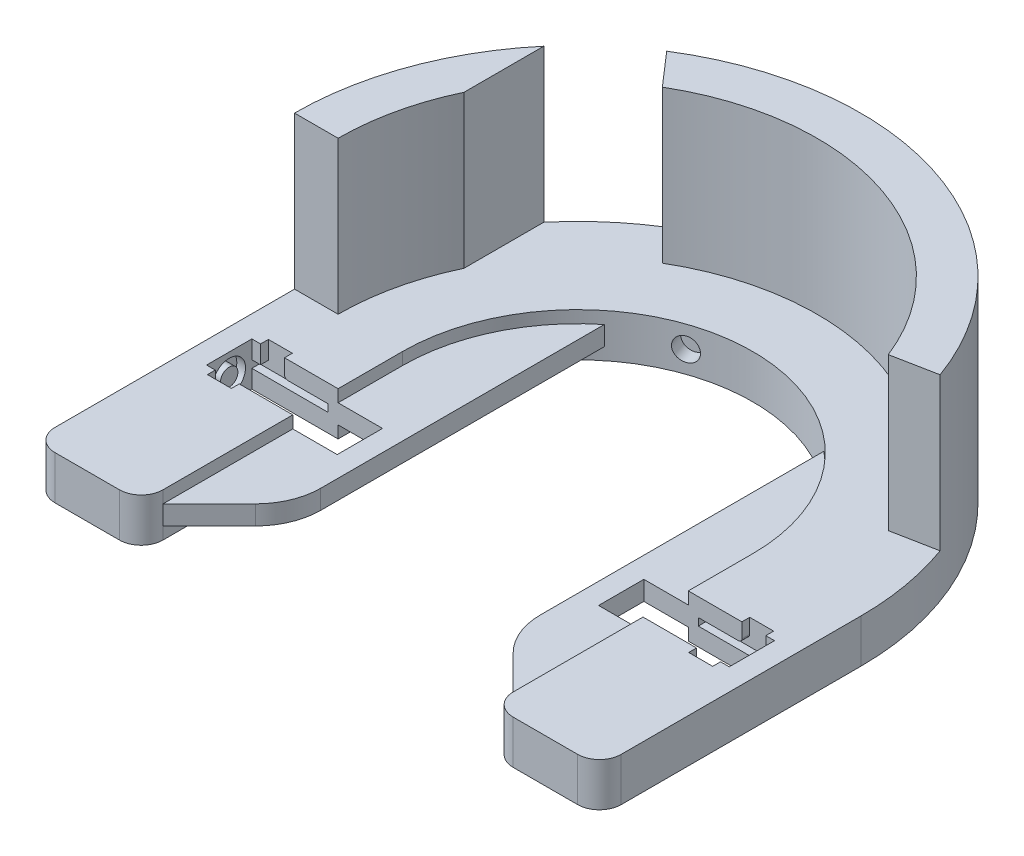
SolidWorks part; units mm, degrees
ref_plane "Front Plane" through (0, 0, 0) normal (0, 0, 1) x (1, 0, 0)
ref_plane "Top Plane" through (0, 0, 0) normal (0, 1, 0) x (1, 0, 0)
ref_plane "Right Plane" through (0, 0, 0) normal (1, 0, 0) x (0, 0, -1)
sketch "Sketch3" plane through (0, 0, 0) normal (0, 1, 0) x (1, 0, 0)
  line L0 (65, 0) -> (65, -55)
  line L1 (-65, 0) -> (65, 0) construction
  line L2 (60, -60) -> (45.2, -60)
  line L3 (40.2, -55) -> (40.2, 0)
  line L4 (25.2, -33.7868) -> (25.2, 31.3209)
  line L5 (29.5934, -44.3934) -> (40.2, -55)
  line L6 (54.9988, 0) -> (54.9988, -60)
  line L7 (0, -55) -> (0, 55) construction
  line L8 (-54.9988, 0) -> (-54.9988, -60)
  line L9 (-29.5934, -44.3934) -> (-40.2, -55)
  line L10 (-25.2, -33.7868) -> (-25.2, 31.3209)
  line L11 (-40.2, -55) -> (-40.2, 0)
  line L12 (-60, -60) -> (-45.2, -60)
  line L13 (-65, 0) -> (-65, -55)
  arc A0 (65, 0) -> (-65, 0) centre (0, 0) ccw
  arc A1 (40.2, 0) -> (-40.2, 0) centre (0, 0) ccw
  arc A2 (60, -60) -> (65, -55) centre (60, -55) ccw
  arc A3 (45.2, -60) -> (40.2, -55) centre (45.2, -55) cw
  arc A4 (25.2, -33.7868) -> (29.5934, -44.3934) centre (40.2, -33.7868) ccw
  arc A5 (-54.9988, 0) -> (54.9988, 0) centre (0, 0) cw
  arc A6 (-25.2, -33.7868) -> (-29.5934, -44.3934) centre (-40.2, -33.7868) cw
  arc A7 (-45.2, -60) -> (-40.2, -55) centre (-45.2, -55) ccw
  arc A8 (-60, -60) -> (-65, -55) centre (-60, -55) cw
  point P12 (65, -60)
  point P16 (40.2, -60)
  point P19 (25.2, -40)
  point P37 (-25.2, -40)
  point P38 (-40.2, -60)
  point P39 (-65, -60)
  dimension "130" = 130
  dimension "D4" = 80.4
  dimension "D8" = 5
  dimension "D9" = 15
  dimension "D10" = 54.9988
  dimension "D2" = 60
  dimension "D3" = 24.8
  dimension "D5" = 15
  dimension "D6" = 5
  dimension "D7" = 15
extrude "Boss-Extrude1" add sketch "Sketch3" along normal mid plane 4.4 contours A1 L1 L10 | L1 L11 L9 A6 L10 | L4 L1 A1 | L1 L4 A4 L5 L3 region at (33.1426, 0, 23.8401) region at (31.3077, 0, -12.105) region at (-31.3077, 0, -12.105) region at (-33.1426, 0, 23.8401)
extrude "Boss-Extrude2" add sketch "Sketch3<3>" along normal mid plane 10 contours A5 L1 A1 | L1 L3 A3 L2 L6 | L1 L8 L12 A7 L11 region at (47.6376, 0, 29.8244) region at (47.5994, 0, -1.2298) region at (-47.6376, 0, 29.8244)
sketch "Sketch3<3>" plane through (0, 0, 0) normal (0, 1, 0) x (1, 0, 0) same geometry as "Sketch3"
extrude "Boss-Extrude3" add sketch "Sketch3<4>" against normal blind 5 and the other way blind 40 contours A0 L1 A5 | L1 L13 A8 L12 L8 | L1 L6 L2 A2 L0 region at (59.9643, 0, 29.7394) region at (59.9994, 0, -1.4534) region at (-59.9643, 0, 29.7394)
sketch "Sketch3<4>" plane through (0, 0, 0) normal (0, 1, 0) x (1, 0, 0) same geometry as "Sketch3"
sketch "Sketch4" plane through (0, 0, 0) normal (1, 0, 0) x (0, 0, -1)
  line L0 (-45, 5) -> (-60, 5)
  line L1 (-60, 5) -> (-60, 40)
  line L2 (-60, 40) -> (0, 40)
  line L3 (0, -5) -> (-55, -5) construction
  line L4 (0, 40) -> (-55, 40) construction
  line L5 (-60, 40) -> (-60, -5) construction
  arc A0 (-45, 5) -> (0, 40) centre (0, -6.4286) cw
  dimension "D2" = 15
  dimension "D1" = 10
extrude "Cut-Extrude1" cut sketch "Sketch4" against normal through all both and the other way through all
sketch "Sketch5" plane through (0, 40, 0) normal (0, 1, 0) x (1, 0, 0)
  line L0 (0, 0) -> (-42.6438, 49.0561) construction
  line L2 (-49.6832, 41.9115) -> (-43.0281, 34.2556) construction
  line L4 (-34.5891, 55.0327) -> (-27.9339, 47.3768)
  line L5 (0, 0) -> (0, 65) construction
  line L6 (-49.6832, 41.9115) -> (-49.6832, 23.5889)
  line L7 (0, 0) -> (63.8058, 12.4026) construction
  line L8 (51.1803, 20.1356) -> (61.1381, 22.0712)
  line L9 (54.9988, 0) -> (54.9988, -45)
  line L10 (54.9988, -45) -> (65, -45)
  line L11 (65, -45) -> (65, 0)
  line L12 (65, -45) -> (65, 0) construction
  line L13 (54.9988, 0) -> (54.9988, -45) construction
  line L14 (54.9988, -45) -> (65, -45) construction
  line L16 (-65, -45) -> (-54.9988, -45)
  line L17 (-65, -45) -> (-65, 0)
  line L18 (-65, 0) -> (-54.9988, 0)
  line L19 (-54.9988, -45) -> (-54.9988, 0)
  arc A0 (65, 0) -> (-65, 0) centre (0, 0) ccw construction
  arc A1 (-49.6832, 41.9115) -> (-34.5891, 55.0327) centre (0, 0) cw
  arc A2 (-43.0281, 34.2556) -> (-27.9339, 47.3768) centre (0, 0) cw
  arc A3 (54.9988, 0) -> (-54.9988, 0) centre (0, 0) ccw construction
  arc A4 (-49.6832, 23.5889) -> (-43.0281, 34.2556) centre (0, 0) cw
  arc A5 (54.9988, 0) -> (-54.9988, 0) centre (0, 0) ccw construction
  arc A6 (61.1381, 22.0712) -> (65, 0) centre (0, 0) cw
  arc A7 (51.1803, 20.1356) -> (54.9988, 0) centre (0, 0) cw
  point P40 (-58.0676, -39.3853)
  point P41 (0, 0)
  dimension "D2" = 20
  dimension "D3" = 10
  dimension "D4" = 120
  dimension "D1" = 41
  dimension "D6" = 10
extrude "Cut-Extrude2" cut sketch "Sketch5" against normal blind 35
ref_axis "Axis1" through (0, 42.25, 0) along (0, -1, 0)
ref_plane "Plane1" through (0, 0, 0) normal (0.3256, 0, 0.9455) x (0, -1, 0)
sketch "Sketch6" plane through (0, 0, 0) normal (0.3256, 0, 0.9455) x (0, -1, 0)
  circle A0 centre (0, 0) radius 2.625
  dimension "D1" = 5.25
extrude "Cut-Extrude3" cut sketch "Sketch6" against normal blind 43.5
sketch "Sketch7" plane through (0, 5, 0) normal (0, 1, 0) x (1, 0, 0)
  line L0 (65, -55) -> (65, 0) construction
  line L1 (30, -14.8) -> (60, -14.8)
  line L2 (30, -14.8) -> (30, -25.2)
  line L3 (30, -25.2) -> (60, -25.2)
  line L4 (60, -14.8) -> (60, -25.2)
  line L6 (0, -55) -> (0, 55) construction
  line L7 (-60, -14.8) -> (-60, -25.2)
  line L8 (-30, -25.2) -> (-60, -25.2)
  line L9 (-30, -14.8) -> (-30, -25.2)
  line L10 (-30, -14.8) -> (-60, -14.8)
  line L11 (60, -60) -> (45.2, -60) construction
  point P7 (60, -20)
  dimension "D1" = 10.4
  dimension "D2" = 30
  dimension "D3" = 5
  dimension "D4" = 40
extrude "Cut-Extrude4" cut sketch "Sketch7" against normal through all
sketch "Sketch8" plane through (0, 0, 0) normal (0, 1, 0) x (1, 0, 0)
  line L0 (60, -25.2) -> (60, -14.8) construction
  line L1 (42.5, -13) -> (60, -13)
  line L2 (42.5, -13) -> (42.5, -27)
  line L3 (42.5, -27) -> (60, -27)
  line L4 (60, -13) -> (60, -27)
  line L6 (60, -14.8) -> (40.2, -14.8) construction
  line L7 (0, -55) -> (0, 55) construction
  line L8 (-60, -13) -> (-60, -27)
  line L9 (-42.5, -27) -> (-60, -27)
  line L10 (-42.5, -13) -> (-42.5, -27)
  line L11 (-42.5, -13) -> (-60, -13)
  dimension "D1" = 14
  dimension "D2" = 17.5
  dimension "D3" = 1.8
extrude "Cut-Extrude5" cut sketch "Sketch8" against normal mid plane 1.7
sketch "Sketch12" plane through (60, 0, 0) normal (-1, 0, 0) x (0, 0, 1)
  circle A0 centre (20, 0) radius 2
  circle A1 centre (20, 0) radius 3.75
  point P3 (21.2896, 0.3952)
  point P4 (0, 0)
  dimension "D1" = 4
  dimension "D2" = 7.5
  dimension "D3" = 20
extrude "Cut-Extrude7" cut sketch "Sketch12" against normal blind 2
sketch "Sketch13" plane through (-60, 0, 0) normal (1, 0, 0) x (0, 0, -1)
  circle A0 centre (-20, 0) radius 3.75
  circle A1 centre (-20, 0) radius 2
  point P3 (0, 0)
  dimension "D1" = 7.5
  dimension "D2" = 4
  dimension "D3" = 20
extrude "Cut-Extrude8" cut sketch "Sketch13" against normal blind 2
sketch "Sketch14" plane through (0, 5, 0) normal (0, 1, 0) x (1, 0, 0)
  line L0 (-60, -14.8) -> (-60, -25.2) construction
  line L1 (-58, -13) -> (-52.5, -13)
  line L2 (-58, -13) -> (-58, -14.8)
  line L3 (-58, -14.8) -> (-52.5, -14.8)
  line L4 (-52.5, -13) -> (-52.5, -14.8)
  line L5 (-40.2, -14.8) -> (-60, -14.8) construction
  line L6 (-58, -25.2) -> (-52.5, -25.2)
  line L7 (-58, -25.2) -> (-58, -27)
  line L8 (-58, -27) -> (-52.5, -27)
  line L9 (-52.5, -25.2) -> (-52.5, -27)
  line L10 (-60, -25.2) -> (-40.2, -25.2) construction
  line L11 (0, -24.75) -> (0, 24.75) construction
  line L12 (52.5, -25.2) -> (52.5, -27)
  line L13 (58, -27) -> (52.5, -27)
  line L14 (58, -25.2) -> (58, -27)
  line L15 (58, -25.2) -> (52.5, -25.2)
  line L16 (52.5, -13) -> (52.5, -14.8)
  line L17 (58, -14.8) -> (52.5, -14.8)
  line L18 (58, -13) -> (58, -14.8)
  line L19 (58, -13) -> (52.5, -13)
  dimension "D1" = 1.8
  dimension "D2" = 5.5
  dimension "D3" = 2
  dimension "D4" = 1.8
  dimension "D6" = 2
extrude "Cut-Extrude9" cut sketch "Sketch14" against normal up to next
fillet "Fillet2" radius 0.75 4 edges at (52.5, 0.85, 26.1) (52.5, 0.85, 13.9) (-52.5, 0.85, 26.1) (-52.5, 0.85, 13.9)
equation "\"D3@Sketch8\"=(\"D1@Sketch8\"-\"D1@Sketch7\")/2"
